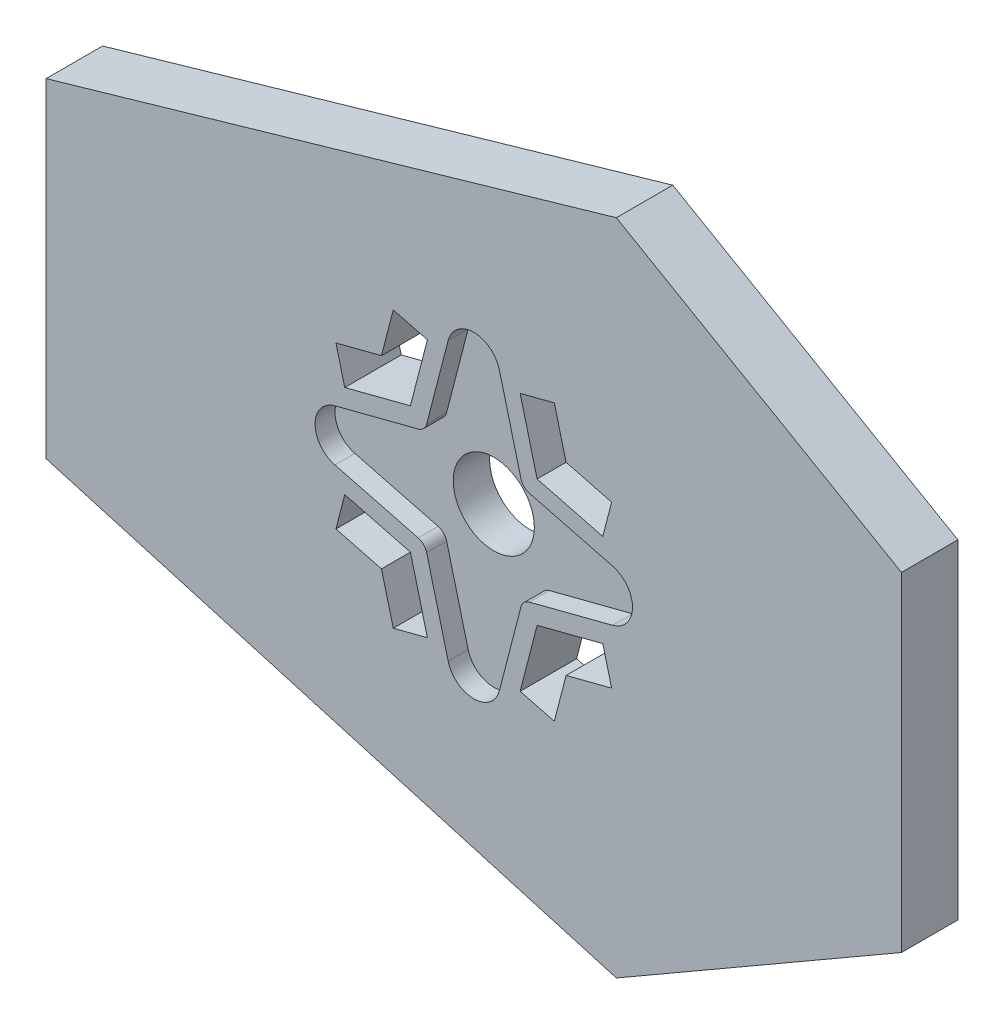
SolidWorks part; units mm, degrees
ref_plane "Front Plane" through (0, 0, 0) normal (0, 0, 1) x (1, 0, 0)
ref_plane "Top Plane" through (0, 0, 0) normal (0, 1, 0) x (1, 0, 0)
ref_plane "Right Plane" through (0, 0, 0) normal (1, 0, 0) x (0, 0, -1)
sketch "Sketch1" plane through (0, 0, 0) normal (0, 0, 1) x (1, 0, 0)
  line L0 (6.9744, -28) -> (-41.5231, -14) construction
  line L1 (-41.5231, 14) -> (-41.5231, -14) construction
  line L2 (-41.5231, 14) -> (6.9744, 28) construction
  line L3 (31.2231, 14) -> (6.9744, 28) construction
  line L4 (31.2231, -14) -> (31.2231, 14) construction
  line L5 (6.9744, -28) -> (31.2231, -14) construction
  line L6 (6.9744, -28) -> (-41.5231, -14)
  line L7 (-41.5231, 14) -> (-41.5231, -14)
  line L8 (-41.5231, 14) -> (6.9744, 28)
  line L9 (31.2231, 14) -> (6.9744, 28)
  line L10 (31.2231, -14) -> (31.2231, 14)
  line L11 (6.9744, -28) -> (31.2231, -14)
  line L20 (-2.9716, -11.813) -> (-1.1403, -4.7276)
  line L21 (-2.9716, -11.813) -> (-1.1403, -4.7276)
  line L22 (-0.4224, -4.0097) -> (6.663, -2.1784)
  line L23 (-0.4224, -4.0097) -> (6.663, -2.1784)
  line L24 (6.663, 2.1784) -> (-0.4224, 4.0097)
  line L25 (6.663, 2.1784) -> (-0.4224, 4.0097)
  line L26 (-1.1403, 4.7276) -> (-2.9716, 11.813)
  line L27 (-1.1403, 4.7276) -> (-2.9716, 11.813)
  line L28 (-7.3284, 11.813) -> (-9.1597, 4.7276)
  line L29 (-7.3284, 11.813) -> (-9.1597, 4.7276)
  line L30 (-9.8776, 4.0097) -> (-16.963, 2.1784)
  line L31 (-9.8776, 4.0097) -> (-16.963, 2.1784)
  line L32 (-16.963, -2.1784) -> (-9.8776, -4.0097)
  line L33 (-16.963, -2.1784) -> (-9.8776, -4.0097)
  line L34 (-9.1597, -4.7276) -> (-7.3284, -11.813)
  line L35 (-9.1597, -4.7276) -> (-7.3284, -11.813)
  circle A0 centre (-5.15, 0) radius 3.45 construction
  circle A1 centre (-5.15, 0) radius 3.45
  arc A9 (6.663, -2.1784) -> (6.663, 2.1784) centre (6.1, 0) ccw
  arc A11 (-2.9716, 11.813) -> (-7.3284, 11.813) centre (-5.15, 11.25) ccw
  arc A13 (-16.963, 2.1784) -> (-16.963, -2.1784) centre (-16.4, 0) ccw
  arc A15 (-7.3284, -11.813) -> (-2.9716, -11.813) centre (-5.15, -11.25) ccw
  arc A17 (6.663, -2.1784) -> (6.663, 2.1784) centre (6.1, 0) ccw
  arc A19 (-2.9716, 11.813) -> (-7.3284, 11.813) centre (-5.15, 11.25) ccw
  arc A21 (-16.963, 2.1784) -> (-16.963, -2.1784) centre (-16.4, 0) ccw
  arc A23 (-7.3284, -11.813) -> (-2.9716, -11.813) centre (-5.15, -11.25) ccw
  arc A30 (-0.4224, -4.0097) -> (-1.1403, -4.7276) centre (-0.1722, -4.9778) ccw
  arc A31 (-0.4224, -4.0097) -> (-1.1403, -4.7276) centre (-0.1722, -4.9778) ccw
  arc A32 (-1.1403, 4.7276) -> (-0.4224, 4.0097) centre (-0.1722, 4.9778) ccw
  arc A33 (-1.1403, 4.7276) -> (-0.4224, 4.0097) centre (-0.1722, 4.9778) ccw
  arc A34 (-9.8776, 4.0097) -> (-9.1597, 4.7276) centre (-10.1278, 4.9778) ccw
  arc A35 (-9.8776, 4.0097) -> (-9.1597, 4.7276) centre (-10.1278, 4.9778) ccw
  arc A36 (-9.1597, -4.7276) -> (-9.8776, -4.0097) centre (-10.1278, -4.9778) ccw
  arc A37 (-9.1597, -4.7276) -> (-9.8776, -4.0097) centre (-10.1278, -4.9778) ccw
  dimension "D1" = 0
extrude "Boss-Extrude1" add sketch "Sketch1" along normal up to surface (3.1 mm away) contours L8 L9 L10 L11 L6 L7 | A1
extrude "Boss-Extrude2" add sketch "Sketch1<3>" along normal up to surface (4.8 mm away) contours L6 L11 L10 L9 L8 L7 A23 A21 A19 A17 region at (-17.0197, -20.118, 0)
sketch "Sketch1<3>" plane through (0, 0, 0) normal (0, 0, 1) x (1, 0, 0) same geometry as "Sketch1"
sketch "Sketch3" plane through (0, 0, 4.8) normal (0, 0, 1) x (1, 0, 0)
  line L0 (-13.0004, 7.8504) -> (-16.8732, 6.8495) construction
  line L1 (-16.8732, 6.8495) -> (-16.1225, 3.9449) construction
  line L2 (-10.5382, 5.3882) -> (-16.1225, 3.9449) construction
  line L3 (-9.0949, 10.9725) -> (-10.5382, 5.3882) construction
  line L4 (-11.9995, 11.7232) -> (-9.0949, 10.9725) construction
  line L5 (-11.9995, 11.7232) -> (-13.0004, 7.8504) construction
  line L6 (-13.0004, 7.8504) -> (-16.8732, 6.8495)
  line L7 (-16.8732, 6.8495) -> (-16.1225, 3.9449)
  line L8 (-10.5382, 5.3882) -> (-16.1225, 3.9449)
  line L9 (-9.0949, 10.9725) -> (-10.5382, 5.3882)
  line L10 (-11.9995, 11.7232) -> (-9.0949, 10.9725)
  line L11 (-11.9995, 11.7232) -> (-13.0004, 7.8504)
extrude "Cut-Extrude1" cut sketch "Sketch3" against normal through all
sketch "Sketch4" plane through (0, 0, 4.8) normal (0, 0, 1) x (1, 0, 0)
  line L0 (-5.15, 13.5) -> (-5.15, -13.5) construction
  line L1 (-18.65, 0) -> (8.35, 0) construction
  arc A0 (-2.9716, 11.813) -> (-7.3284, 11.813) centre (-5.15, 11.25) ccw construction
  arc A1 (-7.3284, -11.813) -> (-2.9716, -11.813) centre (-5.15, -11.25) ccw construction
  arc A2 (-16.963, 2.1784) -> (-16.963, -2.1784) centre (-16.4, 0) ccw construction
  arc A3 (6.663, -2.1784) -> (6.663, 2.1784) centre (6.1, 0) ccw construction
ref_plane "Plane1" through (-5.15, 0, 0) normal (-1, 0, 0) x (0, -1, 0)
ref_plane "Plane2" through (0, 0, 0) normal (0, -1, 0) x (1, 0, 0)
mirror "Mirror1" about plane through (-5.15, 0, 0) normal (-1, 0, 0) of "Cut-Extrude1"
mirror "Mirror2" about plane through (0, 0, 0) normal (0, -1, 0) of "Cut-Extrude1", "Mirror1"
